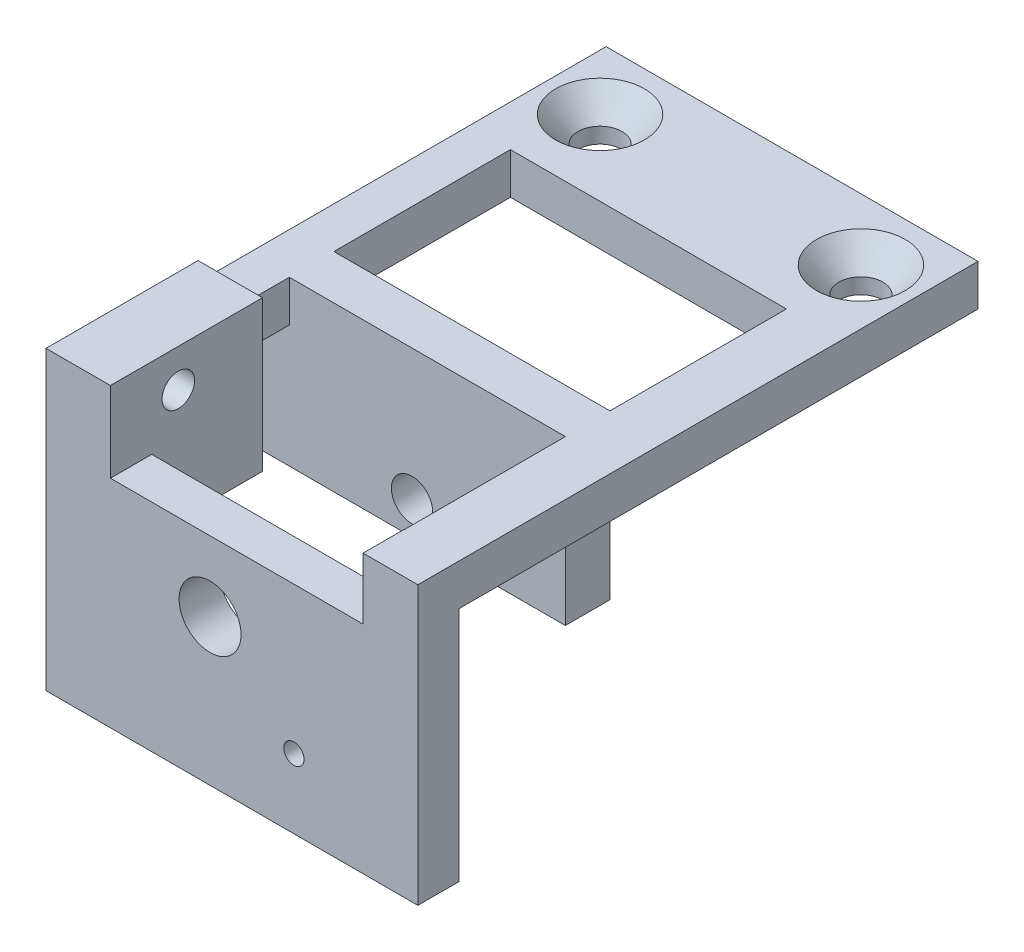
SolidWorks part; units mm, degrees
material "ABS"
ref_plane "Front Plane" through (0, 0, 0) normal (0, 0, 1) x (1, 0, 0)
ref_plane "Top Plane" through (0, 0, 0) normal (0, 1, 0) x (1, 0, 0)
ref_plane "Right Plane" through (0, 0, 0) normal (1, 0, 0) x (0, 0, -1)
sketch "Sketch1" plane through (0, 0, 0) normal (0, 0, 1) x (1, 0, 0)
  line L0 (0, 8.8442) -> (12.8921, -2.9343) construction
  line L1 (23.5226, 29.0697) -> (31.9421, 29.0697)
  line L2 (-25.2079, 8.8442) -> (-25.2079, -13.6023)
  line L3 (-25.2079, -13.6023) -> (31.9421, -13.6023)
  line L4 (31.9421, 29.0697) -> (31.9421, -13.6023)
  line L6 (-25.2079, 8.8442) -> (-25.2079, 31.9582)
  line L7 (-25.2079, 31.9582) -> (-18.8579, 31.9582)
  line L11 (23.5226, 22.6565) -> (23.5226, 29.0697)
  line L12 (-18.8579, 31.9582) -> (-15.3109, 31.9582)
  line L14 (-15.3109, 31.9582) -> (-15.3109, 22.6565)
  line L15 (-15.3109, 22.6565) -> (-15.3109, 19.6203)
  line L16 (-15.3109, 19.6203) -> (23.5226, 19.6203)
  line L17 (23.5226, 19.6203) -> (23.5226, 22.6565)
  circle A0 centre (12.8921, -2.9343) radius 1.5615
  circle A1 centre (0, 8.8442) radius 4.7625
  dimension "D5" = 9.525
  dimension "D1" = 23.114
  dimension "D2" = 57.15
  dimension "D3" = 42.672
  dimension "D4" = 6.35
  dimension "D6" = 19.05
  dimension "D7" = 10.668
  dimension "D8" = 17.4625
extrude "Boss-Extrude1" add sketch "Sketch1" against normal blind 6.35
sketch "Sketch2" plane through (0, 0, 0) normal (0, 0, 1) x (1, 0, 0)
  line L0 (-25.2079, 31.9582) -> (-25.2079, -13.6023) construction
  line L1 (-18.8579, 31.9582) -> (-25.2079, 31.9582)
  line L3 (-18.8579, 8.8442) -> (-25.2079, 8.8442)
  line L4 (-25.2079, 31.9582) -> (-25.2079, 8.8442)
  line L6 (-15.3109, 31.9582) -> (-25.2079, 31.9582)
  line L7 (-15.3109, 31.9582) -> (-15.3109, 8.8442)
  line L8 (-15.3109, 8.8442) -> (-25.2079, 8.8442)
  line L9 (-25.2079, 31.9582) -> (-25.2079, 8.8442)
  line M4 (-15.3109, 31.9582) -> (-25.2079, 31.9582)
  line M5 (-25.2079, 31.9582) -> (-25.2079, -13.6023)
  line M15 (-15.3109, 19.6203) -> (-15.3109, 31.9582)
  dimension "D1" = 23.114
extrude "Boss-Extrude2" add sketch "Sketch2" against normal blind 23.368 contours L8 L7 L3 M15 M4 M5 region at (-20.2594, 20.4012, 0)
sketch "Sketch3" plane through (0, 29.0697, 0) normal (0, 1, 0) x (1, 0, 0)
  line L0 (-25.2079, 23.368) -> (-25.2079, 0) construction
  line L1 (-18.8579, 0) -> (-25.2079, 0)
  line L2 (-18.8579, 0) -> (-18.8579, 78.34)
  line L3 (-18.8579, 78.34) -> (-25.2079, 78.34)
  line L4 (-25.2079, 0) -> (-25.2079, 78.34)
  line L5 (31.9421, 0) -> (23.5601, 0)
  line L6 (31.9421, 0) -> (31.9421, 78.34)
  line L7 (31.9421, 78.34) -> (23.5601, 78.34)
  line L8 (23.5601, 0) -> (23.5601, 78.34)
  dimension "D2" = 8.382
  dimension "D3" = 78.34
  dimension "D4" = 78.34
extrude "Boss-Extrude3" add sketch "Sketch3" against normal blind 6.35
sketch "Sketch4" plane through (-25.2079, 0, 0) normal (-1, 0, 0) x (0, 0, 1)
  circle A0 centre (-10.4375, 26.1623) radius 2.5
  dimension "D1" = 5
extrude "Cut-Extrude1" cut sketch "Sketch4" against normal up to next
sketch "Sketch5" plane through (0, 29.0697, 0) normal (0, 1, 0) x (1, 0, 0)
  line L0 (31.9421, 78.34) -> (31.9421, 0) construction
  line L2 (-25.2079, 78.34) -> (-25.2079, 65.0226)
  line L3 (-25.2079, 65.0226) -> (31.9421, 65.0226)
  line L4 (31.9421, 78.34) -> (31.9421, 65.0226)
  line L5 (-25.2079, 78.34) -> (-25.2079, 23.368) construction
  line L7 (31.9421, 65.0226) -> (31.9421, 132.9282) construction
  line L9 (-25.2079, 78.34) -> (-25.2079, 86.0813)
  line L10 (-25.2079, 86.0813) -> (31.9421, 86.0813)
  line L11 (31.9421, 78.34) -> (31.9421, 86.0813)
extrude "Boss-Extrude4" add sketch "Sketch5" against normal blind 6.35
hole_wizard "CSK for 1/4 Flat Head Machine Screw1" positions "Sketch6" profile "Sketch7" countersink size "1/4" standard "ANSI Inch" end condition through all
sketch "Sketch6" plane through (0, 29.0697, 0) normal (0, 1, 0) x (1, 0, 0)
  point P0 (-16.6611, 76.5965)
  point P2 (23.4347, 76.5965)
sketch "Sketch7" plane through (-16.6611, 29.0697, -76.5965) normal (1, 0, 0) x (0, 0, 1)
  line L0 (0, 0) -> (0, 42.672)
  line L1 (0, 42.672) -> (3.3782, 42.672)
  line L2 (3.3782, 42.672) -> (3.3782, 3.9592)
  line L3 (3.3782, 3.9592) -> (6.8199, 0)
  line L5 (6.8199, 0) -> (0, 0)
  line L6 (-3.3782, 3.9592) -> (-6.8199, 0) construction
  line L11 (0, -6.35) -> (0, 107.95) construction
  dimension "Thru Hole Dia." = 6.7564
  dimension "Thru Hole Depth" = 42.672
  dimension "Near C'Sink Dia." = 13.6398
  dimension "Near C'Sink Angle" = 82
sketch "Sketch8" plane through (0, 29.0697, 0) normal (0, 1, 0) x (1, 0, 0)
  line L0 (-25.2079, 86.0813) -> (-25.2079, 23.368) construction
  line L10 (-25.2079, 37.893) -> (23.5601, 37.893)
  line L11 (23.5601, 65.0226) -> (23.5601, 6.35) construction
  line L12 (23.5601, 37.893) -> (23.5601, 31.05)
  line L13 (23.5601, 31.05) -> (-25.2079, 31.05)
  line L14 (-25.2079, 37.893) -> (-25.2079, 31.05)
extrude "Boss-Extrude5" add sketch "Sketch8" against normal blind 25.146
sketch "Sketch10" plane through (0, 0, -37.893) normal (0, 0, -1) x (-1, 0, 0)
  circle A0 centre (0, 8.8442) radius 3.175
  dimension "D1" = 6.35
extrude "Cut-Extrude2" cut sketch "Sketch10" against normal up to next
